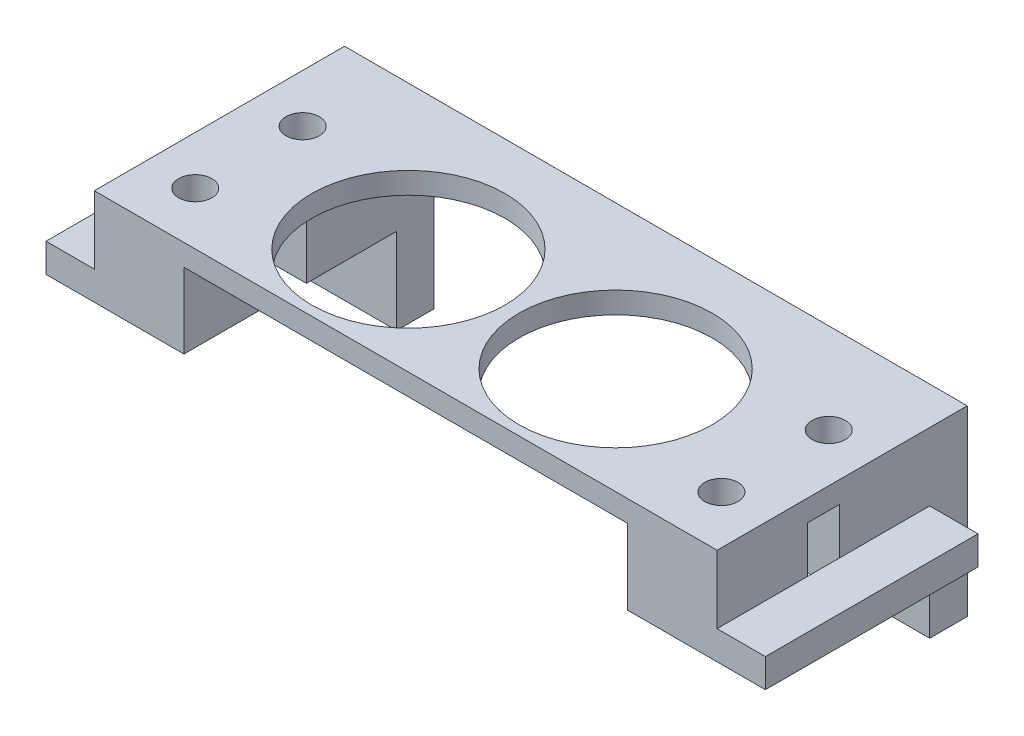
SolidWorks part; units mm, degrees
ref_plane "Front Plane" through (0, 0, 0) normal (0, 0, 1) x (1, 0, 0)
ref_plane "Top Plane" through (0, 0, 0) normal (0, 1, 0) x (1, 0, 0)
ref_plane "Right Plane" through (0, 0, 0) normal (1, 0, 0) x (0, 0, -1)
sketch "Sketch2" plane through (0, 0, 0) normal (0, 1, 0) x (1, 0, 0)
  line L0 (-24.5, 5) -> (-24.5, -5) construction
  line L1 (-29, 9.9) -> (29, 9.9)
  line L2 (-29, 9.9) -> (-29, -9.9)
  line L3 (-29, -9.9) -> (29, -9.9)
  line L4 (29, 9.9) -> (29, -9.9)
  line L5 (-29, 9.9) -> (29, -9.9) construction
  line L6 (-29, -9.9) -> (29, 9.9) construction
  line L7 (-24.5, -5) -> (24.5, -5) construction
  line L8 (24.5, -5) -> (24.5, 5) construction
  line L9 (24.5, 5) -> (-24.5, 5) construction
  line L10 (-20.65, 9.9) -> (-20.65, -9.9) construction
  line L15 (20.65, 9.9) -> (20.65, -9.9) construction
  line L16 (-20.65, 0) -> (20.65, 0) construction
  circle A0 centre (-9.65, 0) radius 9
  circle A1 centre (-24.5, 5) radius 1.55
  circle A2 centre (-24.5, -5) radius 1.55
  circle A3 centre (24.5, 5) radius 1.55
  circle A4 centre (24.5, -5) radius 1.55
  circle A5 centre (9.65, 0) radius 9
  point P0 (0, 0)
  point P16 (-24.5, 0)
  point P17 (0, 5)
  point P27 (0, 0)
  dimension "D1" = 18
  dimension "D2" = 3.1
  dimension "D9" = 41.3
  dimension "D10" = 11
  dimension "D3" = 4.5
  dimension "D4" = 10
  dimension "D5" = 49
  dimension "D6" = 19.8
  dimension "D7" = 11
extrude "Boss-Extrude1" add sketch "Sketch2" along normal blind 2 contours L4 L1 L2 L3 A4 A3 A2 A1 A0 region at (0, 0, 0)
sketch "Sketch3" plane through (0, 0, 0) normal (0, -1, 0) x (1, 0, 0)
  line L0 (-20.65, 9.9) -> (-20.65, -9.9)
  line L1 (-29, 9.9) -> (29, 9.9) construction
  line L2 (-29, -9.9) -> (29, -9.9) construction
  line L3 (-20.65, -9.9) -> (-29, -9.9)
  line L4 (-29, -9.9) -> (-29, 9.9)
  line L5 (-29, 9.9) -> (-20.65, 9.9)
  line L6 (20.65, 9.9) -> (20.65, -9.9)
  line L7 (20.65, -9.9) -> (29, -9.9)
  line L8 (29, -9.9) -> (29, 9.9)
  line L9 (29, 9.9) -> (20.65, 9.9)
  line L10 (-29, 9.9) -> (29, 9.9) construction
  line L12 (-29, 1.5) -> (-20.65, 1.5)
  line L13 (-29, 1.5) -> (-29, -1.5)
  line L14 (-29, -1.5) -> (-20.65, -1.5)
  line L15 (-20.65, 1.5) -> (-20.65, -1.5)
  line L16 (20.65, 1.5) -> (29, 1.5)
  line L17 (20.65, 1.5) -> (20.65, -1.5)
  line L18 (20.65, -1.5) -> (29, -1.5)
  line L19 (29, 1.5) -> (29, -1.5)
  circle A0 centre (-24.5, -5) radius 1.55
  circle A1 centre (-24.5, 5) radius 1.55
  circle A2 centre (24.5, -5) radius 1.55
  circle A3 centre (24.5, 5) radius 1.55
  point P43 (20.65, 0)
  point P44 (-20.65, 0)
  circle M5 centre (24.5, 5) radius 1.55
  circle M6 centre (24.5, -5) radius 1.55
  circle M7 centre (-24.5, 5) radius 1.55
  circle M8 centre (-24.5, -5) radius 1.55
  line M13 (29, -9.9) -> (29, 9.9)
  line M14 (29, 9.9) -> (-29, 9.9)
  line M15 (-29, 9.9) -> (-29, -9.9)
  line M16 (-29, -9.9) -> (29, -9.9)
  dimension "D1" = 3
extrude "Boss-Extrude2" add sketch "Sketch3" along normal blind 7 contours L12 L0 M15 M14 M7 | L14 L0 M15 M16 M8 | L6 L16 L8 M14 M5 | L18 L6 M16 M13 M6 region at (-20.7684, 0, 5.7) region at (24.825, 0, 9.7816) region at (-20.7684, 0, -5.7) region at (24.825, 0, -1.6184)
sketch "Sketch6" plane through (0, 2, 0) normal (0, 1, 0) x (1, 0, 0)
  line L1 (29, 9.9) -> (-29, 9.9)
  line L2 (29, 9.9) -> (29, 13.4)
  line L3 (29, 13.4) -> (-29, 13.4)
  line L4 (-29, 9.9) -> (-29, 13.4)
  line L5 (20.65, 9.9) -> (-20.65, 9.9)
  line L6 (20.65, 9.9) -> (20.65, 13.4)
  line L7 (20.65, 13.4) -> (-20.65, 13.4)
  line L8 (-20.65, 9.9) -> (-20.65, 13.4)
  line M12 (29, 9.9) -> (-29, 9.9)
  line M14 (-29, -9.9) -> (29, -9.9)
  dimension "D1" = 3.5
extrude "Boss-Extrude4" add sketch "Sketch6" against normal up to surface (2 mm away) contours L6 L2 L3 M12 | L8 L3 L4 M12 | L8 L1 L6 L3 | M14 | M14 | M14 region at (24.825, 2, -11.65) region at (0, 2, -11.65) region at (-24.825, 2, -11.65) up to face at (-9.65, 0, 9)
extrude "Boss-Extrude5" add sketch "Sketch6<3>" against normal blind 17 contours L6 L2 L3 M12 | L8 L3 L4 M12 region at (24.825, 2, -11.65) region at (-24.825, 2, -11.65)
sketch "Sketch6<3>" plane through (0, 2, 0) normal (0, 1, 0) x (1, 0, 0) same geometry as "Sketch6"
extrude "Boss-Extrude6" add sketch "Sketch6<4>" against normal up to surface (9 mm away) contours M14 | M14 | L6 L2 L3 M12 | L8 L3 L4 M12 region at (24.825, 2, -11.65) region at (-24.825, 2, -11.65) up to face at (24.825, -7, -5.7)
sketch "Sketch6<4>" plane through (0, 2, 0) normal (0, 1, 0) x (1, 0, 0) same geometry as "Sketch6"
sketch "Sketch7" plane through (0, -7, 0) normal (0, -1, 0) x (1, 0, 0)
  line L1 (29, 9.9) -> (33.5, 9.9)
  line L2 (29, 9.9) -> (29, -9.9)
  line L3 (29, -9.9) -> (33.5, -9.9)
  line L4 (33.5, 9.9) -> (33.5, -9.9)
  line L5 (-29, 9.9) -> (-33.5, 9.9)
  line L6 (-29, 9.9) -> (-29, -9.9)
  line L7 (-29, -9.9) -> (-33.5, -9.9)
  line L8 (-33.5, 9.9) -> (-33.5, -9.9)
  line L9 (29, 1.5) -> (29, 9.9) construction
  dimension "D1" = 4.5
extrude "Boss-Extrude7" add sketch "Sketch7" against normal blind 2.675
